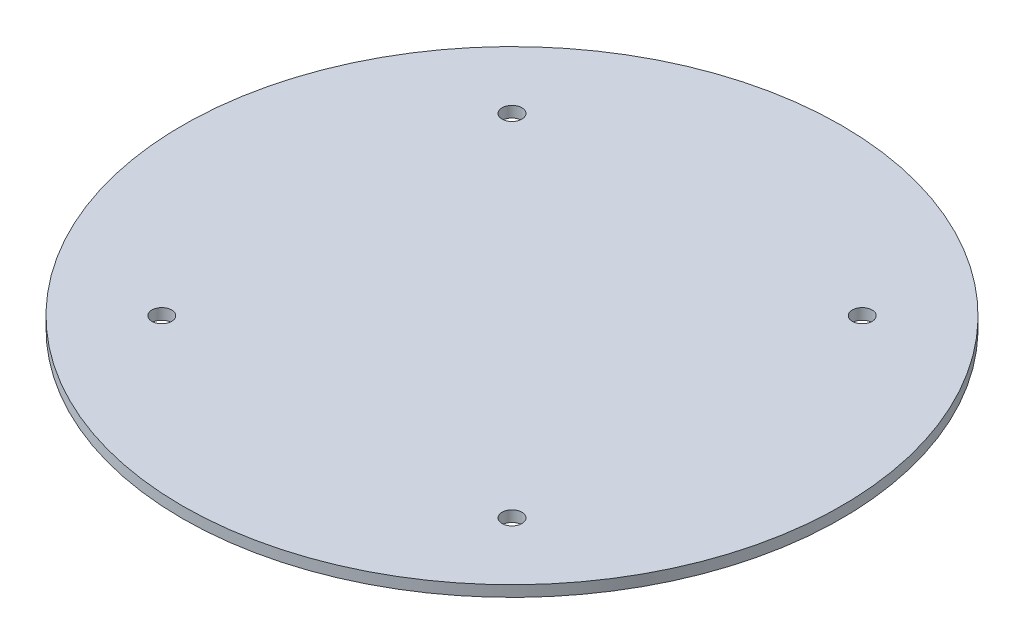
SolidWorks part; units mm, degrees
ref_plane "Front Plane" through (0, 0, 0) normal (0, 0, 1) x (1, 0, 0)
ref_plane "Top Plane" through (0, 0, 0) normal (0, 1, 0) x (1, 0, 0)
ref_plane "Right Plane" through (0, 0, 0) normal (1, 0, 0) x (0, 0, -1)
sketch "Sketch1" plane through (0, 0, 0) normal (0, 1, 0) x (1, 0, 0)
  line L1 (-40.49, -40.49) -> (40.49, -40.49) construction
  line L2 (-40.49, -40.49) -> (-40.49, 40.49) construction
  line L3 (-40.49, 40.49) -> (40.49, 40.49) construction
  line L4 (40.49, -40.49) -> (40.49, 40.49) construction
  line L5 (-40.49, -40.49) -> (40.49, 40.49) construction
  line L6 (-40.49, 40.49) -> (40.49, -40.49) construction
  circle A0 centre (0, 0) radius 76.2
  circle A1 centre (40.49, 40.49) radius 2.286
  circle A2 centre (40.49, -40.49) radius 2.286
  circle A3 centre (-40.49, -40.49) radius 2.286
  circle A4 centre (-40.49, 40.49) radius 2.286
  dimension "D1" = 152.4
  dimension "D3" = 4.572
  dimension "D4" = 4.572
  dimension "D5" = 4.572
  dimension "D6" = 4.572
  dimension "D2" = 80.98
extrude "Boss-Extrude2" add sketch "Sketch1" along normal blind 2.54
